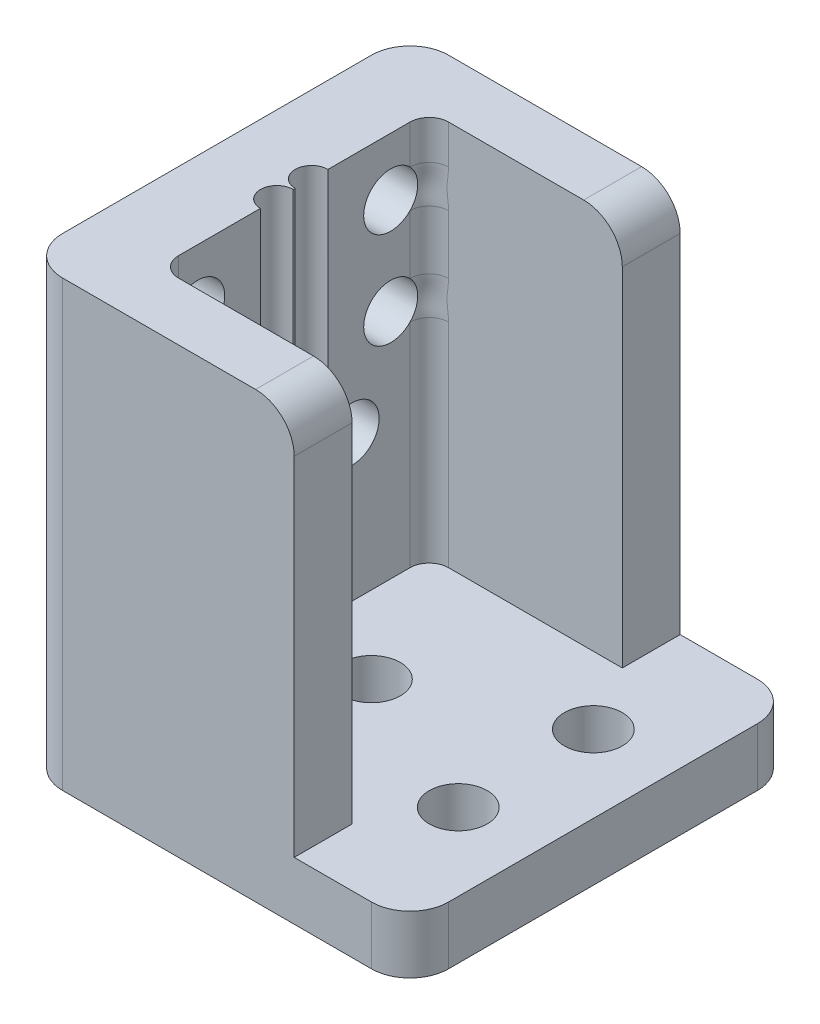
SolidWorks part; units mm, degrees
ref_plane "Front Plane" through (0, 0, 0) normal (0, 0, 1) x (1, 0, 0)
ref_plane "Top Plane" through (0, 0, 0) normal (0, 1, 0) x (1, 0, 0)
ref_plane "Right Plane" through (0, 0, 0) normal (1, 0, 0) x (0, 0, -1)
sketch "Sketch1" plane through (0, 0, 0) normal (0, 1, 0) x (1, 0, 0)
  line L1 (0, 0) -> (16, 0)
  line L2 (0, 0) -> (0, -20)
  line L3 (0, -20) -> (16, -20)
  line L4 (16, 0) -> (16, -20)
  circle A0 centre (4, -10) radius 1.5
  circle A1 centre (12, -13.5) radius 1.5
  circle A2 centre (12, -6.5) radius 1.5
  dimension "D5" = 3
  dimension "D6" = 3
  dimension "D7" = 3
  dimension "D1" = 20
  dimension "D2" = 16
  dimension "D3" = 4
  dimension "D4" = 4
  dimension "D8" = 7
  dimension "D9" = 8
  dimension "D10" = 6.5
  dimension "D11" = 10
extrude "Boss-Extrude1" add sketch "Sketch1" along normal blind 3
sketch "Sketch2" plane through (0, 3, 0) normal (0, 1, 0) x (1, 0, 0)
  line L0 (16, 0) -> (0, 0) construction
  line L1 (0, -20) -> (-4, -20)
  line L2 (0, -20) -> (0, 0)
  line L3 (0, 0) -> (-4, 0)
  line L4 (-4, -20) -> (-4, 0)
  line L5 (0, 0) -> (0, -20) construction
  line L6 (0, -20) -> (16, -20) construction
  line L7 (16, -20) -> (16, 0) construction
  dimension "D1" = 0
  dimension "D2" = 4
  dimension "D3" = 0
  dimension "D4" = 16
extrude "Boss-Extrude3" add sketch "Sketch2" along normal blind 20 separate body
sketch "Sketch3" plane through (0, 3, 0) normal (0, -1, 0) x (-1, 0, 0)
  line L1 (4, -20) -> (0, -20)
  line L2 (4, -20) -> (4, 0)
  line L3 (4, 0) -> (0, 0)
  line L4 (0, -20) -> (0, 0)
extrude "Boss-Extrude4" add sketch "Sketch3" along normal blind 3
fillet "Fillet2" radius 2 2 edges at (16, 1.5, 0) (16, 1.5, 20)
sketch "Sketch4" plane through (0, 3, 0) normal (0, 1, 0) x (1, 0, 0)
  line L1 (0, -20) -> (10, -20)
  line L2 (0, -20) -> (0, -17)
  line L3 (0, -17) -> (10, -17)
  line L4 (10, -20) -> (10, -17)
  line L5 (0, 0) -> (10, 0)
  line L6 (0, 0) -> (0, -3)
  line L7 (0, -3) -> (10, -3)
  line L8 (10, 0) -> (10, -3)
  dimension "D1" = 3
  dimension "D2" = 3
  dimension "D3" = 10
  dimension "D4" = 10
extrude "Boss-Extrude5" add sketch "Sketch4" along normal blind 20
sketch "Sketch5" plane through (0, 0, 0) normal (1, 0, 0) x (0, 0, -1)
  line L0 (-17, 23) -> (-3, 23) construction
  line L1 (-3, 23) -> (-3, 3) construction
  line L2 (-17, 23) -> (-17, 3) construction
  circle A0 centre (-13, 10.5) radius 1.4
  circle A1 centre (-7, 10.5) radius 1.4
  dimension "D1" = 2.8
  dimension "D2" = 2.8
  dimension "D4" = 12.5
  dimension "D3" = 12.5
  dimension "D5" = 4
  dimension "D6" = 4
extrude "Cut-Extrude1" cut sketch "Sketch5" against normal blind 15
sketch "Sketch6" plane through (0, 23, 0) normal (0, 1, 0) x (1, 0, 0)
  line L0 (0, -17) -> (0, -3) construction
  line L1 (10, -17) -> (0, -17) construction
  line L2 (0, -3) -> (10, -3) construction
  circle A0 centre (0, -9.1) radius 0.85
  circle A1 centre (0, -10.9) radius 0.85
  dimension "D1" = 1.7
  dimension "D2" = 1.7
  dimension "D3" = 6.1
  dimension "D4" = 6.1
extrude "Cut-Extrude2" cut sketch "Sketch6" against normal blind 20
sketch "Sketch7" plane through (0, 0, 0) normal (1, 0, 0) x (0, 0, -1)
  line L0 (-17, 23) -> (-11.75, 23) construction
  line L1 (-8.25, 23) -> (-3, 23) construction
  line L2 (-17, 23) -> (-17, 3) construction
  line L3 (-3, 23) -> (-3, 3) construction
  circle A0 centre (-5, 15) radius 1.4
  circle A1 centre (-15, 15) radius 1.4
  circle A2 centre (-15, 20) radius 1.4
  circle A3 centre (-5, 20) radius 1.4
  dimension "D1" = 2.8
  dimension "D2" = 2.8
  dimension "D3" = 8
  dimension "D4" = 8
  dimension "D5" = 2
  dimension "D6" = 2
  dimension "D7" = 2
extrude "Cut-Extrude3" cut sketch "Sketch7" against normal blind 10
fillet "Fillet3" radius 2 4 edges at (-4, 11.5, 20) (-4, 11.5, 0) (10, 23, 18.5) (10, 23, 1.5)
fillet "Fillet4" radius 1 2 edges at (0, 13, 17) (0, 13, 3)
equation "\"D10@Sketch1\"=10-3.5"
